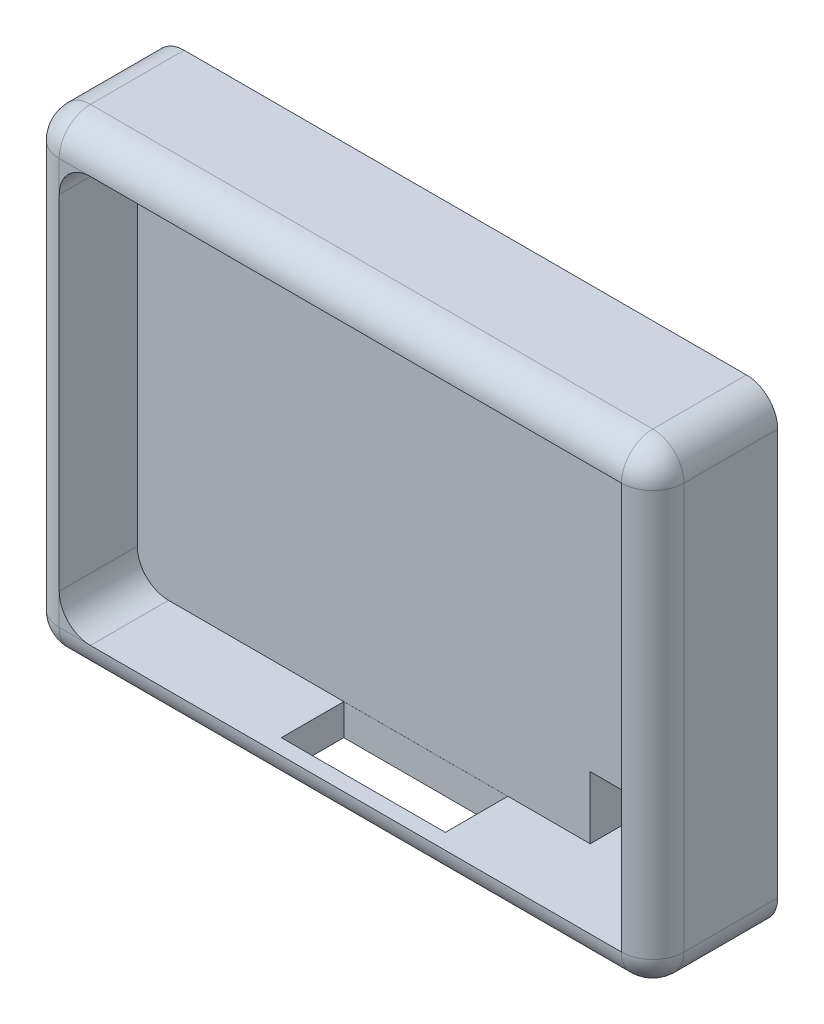
SolidWorks part; units mm, degrees
ref_plane "前视基准面" through (0, 0, 0) normal (0, 0, 1) x (1, 0, 0)
ref_plane "上视基准面" through (0, 0, 0) normal (0, 1, 0) x (1, 0, 0)
ref_plane "右视基准面" through (0, 0, 0) normal (1, 0, 0) x (0, 0, -1)
sketch "Sketch1" plane through (0, 0, 0) normal (0, 0, 1) x (1, 0, 0)
  line L0 (20, 30) -> (20, 0) construction
  line L1 (0, 0) -> (40, 0)
  line L2 (0, 0) -> (0, 30)
  line L3 (0, 30) -> (40, 30)
  line L4 (40, 0) -> (40, 30)
  line L5 (0, 15) -> (40, 15) construction
  point P9 (20, 15)
  dimension "D1" = 40
  dimension "D2" = 30
extrude "Boss-Extrude1" add sketch "Sketch1" along normal blind 8
sketch "Sketch2" plane through (0, 0, 8) normal (0, 0, 1) x (1, 0, 0)
  line L0 (0, 30) -> (40, 0) construction
  line L1 (0, 0) -> (40, 0) construction
  line L2 (40, 0) -> (40, 30) construction
  line L3 (40, 30) -> (0, 0) construction
  line L5 (2, 28) -> (38, 28)
  line L6 (2, 28) -> (2, 2)
  line L7 (2, 2) -> (38, 2)
  line L8 (38, 28) -> (38, 2)
  line L9 (2, 28) -> (38, 2) construction
  line L10 (2, 2) -> (38, 28) construction
  point P11 (20, 15)
  dimension "D1" = 36
  dimension "D2" = 26
extrude "Cut-Extrude1" cut sketch "Sketch2" against normal blind 5
fillet "Fillet1" radius 2 2 edges at (2, 28, 5.5) (2, 2, 5.5)
fillet "Fillet2" radius 2 8 edges at (20, 0, 8) (40, 15, 8) (20, 30, 8) (0, 15, 8) (0, 0, 4) (40, 0, 4) (40, 30, 4) (0, 30, 4)
sketch "Sketch3" plane through (0, 0, 3) normal (0, 0, 1) x (1, 0, 0)
  line L1 (38, 2) -> (31, 2)
  line L2 (38, 2) -> (38, 6)
  line L3 (38, 6) -> (31, 6)
  line L4 (31, 2) -> (31, 6)
  dimension "D1" = 7
  dimension "D2" = 4
extrude "Cut-Extrude2" cut sketch "Sketch3" against normal up to surface (3 mm away) up to face at (20, 15, 0)
sketch "Sketch6" plane through (0, 2, 0) normal (0, 1, 0) x (1, 0, 0)
  line L0 (31, -3) -> (38, -3) construction
  line L1 (38, 0) -> (38, -8) construction
  line L2 (38, -3) -> (38, -4.7524) construction
  line L3 (38, -4.7524) -> (20.4758, -4.7524) construction
  line L4 (4, -3) -> (31, -3) construction
  line L5 (25.7258, -6.5024) -> (25.7258, -7.0042) construction
  line L6 (15.2258, -3.0024) -> (25.7258, -3.0024)
  line L7 (15.2258, -3.0024) -> (15.2258, -6.5024)
  line L9 (25.7258, -3.0024) -> (25.7258, -6.5024)
  line L10 (15.2258, -3.0024) -> (25.7258, -6.5024) construction
  line L11 (15.2258, -6.5024) -> (25.7258, -3.0024) construction
  line L12 (25.7258, -7.0042) -> (15.2258, -7.0042) construction
  line L13 (15.2258, -7.0042) -> (15.2258, -6.5024) construction
  line L14 (15.2258, -6.5024) -> (15.2258, -7.0042)
  line L15 (15.2258, -7.0042) -> (25.7258, -7.0042)
  line L16 (25.7258, -7.0042) -> (25.7258, -6.5024)
  point P13 (0, 0)
  point P16 (0, 0)
  point P17 (0, 0)
  point P18 (0, 0)
  dimension "D2" = 10.5
extrude "Cut-Extrude3" cut sketch "Sketch6" against normal up to surface (2 mm away) up to face at (20, 0, 3)
